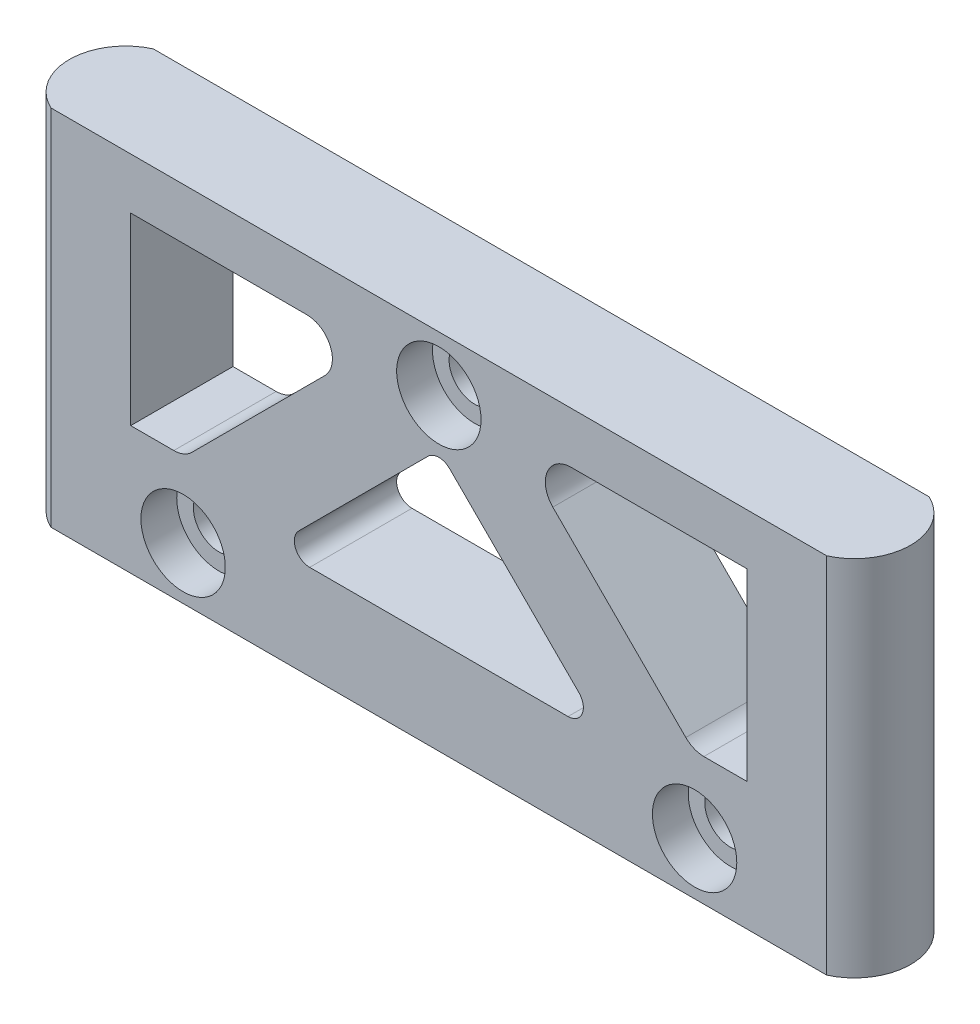
SolidWorks part; units mm, degrees
ref_plane "Front Plane" through (0, 0, 0) normal (0, 0, 1) x (1, 0, 0)
ref_plane "Top Plane" through (0, 0, 0) normal (0, 1, 0) x (1, 0, 0)
ref_plane "Right Plane" through (0, 0, 0) normal (1, 0, 0) x (0, 0, -1)
sketch "Sketch2" plane through (0, 0, 0) normal (0, 0, 1) x (1, 0, 0)
  line L0 (-100, 0) -> (0, 0) construction
  line L1 (-100, 10.25) -> (0, 10.25)
  line L2 (-100, -10.25) -> (0, -10.25)
  line L3 (0, 0) -> (-50, 50) construction
  line L4 (-7.2478, -7.2478) -> (-57.2478, 42.7522)
  line L5 (7.2478, 7.2478) -> (-42.7522, 57.2478)
  line L6 (-100, 0) -> (-50, 50) construction
  line L7 (-107.2478, 7.2478) -> (-57.2478, 57.2478)
  line L8 (-92.7522, -7.2478) -> (-42.7522, 42.7522)
  arc A0 (-100, 10.25) -> (-100, -10.25) centre (-100, 0) ccw
  arc A1 (0, -10.25) -> (0, 10.25) centre (0, 0) ccw
  arc A2 (-7.2478, -7.2478) -> (7.2478, 7.2478) centre (0, 0) ccw
  arc A3 (-42.7522, 57.2478) -> (-57.2478, 42.7522) centre (-50, 50) ccw
  arc A4 (-107.2478, 7.2478) -> (-92.7522, -7.2478) centre (-100, 0) ccw
  arc A5 (-42.7522, 42.7522) -> (-57.2478, 57.2478) centre (-50, 50) ccw
  point P3 (-50, 0)
  point P8 (-25, 25)
  point P15 (-75, 25)
  dimension "D1" = 100
  dimension "D2" = 20.5
  dimension "D3" = 45
  dimension "D4" = 45
extrude "Boss-Extrude4" add sketch "Sketch2" along normal blind 20 contours A4 L2 A2 L4 L1 L8 | A0 A4 L8 L1 | A3 L7 A0 L1 L8 L4 | L8 A5 A3 L4 | A5 L8 L4 L1 A1 L5 | L4 A2 A1 L1 region at (-74.0722, 27.272, 0) region at (-96.1173, 1.6083, 0) region at (-50, -1.0132, 0) region at (-25.9278, 27.272, 0) region at (-3.8827, 1.6083, 0) region at (-50, 49.2802, 0)
sketch "Sketch3" plane through (0, 0, 0) normal (0, 0, -1) x (-1, 0, 0)
  line L0 (57.2478, 57.2478) -> (107.2478, 7.2478)
  line L1 (57.2478, 57.2478) -> (107.2478, 7.2478)
  line L2 (100, -10.25) -> (0, -10.25)
  line L3 (100, -10.25) -> (0, -10.25)
  line L4 (-7.2478, 7.2478) -> (42.7522, 57.2478)
  line L5 (-7.2478, 7.2478) -> (42.7522, 57.2478)
  circle A0 centre (0, 0) radius 8.25
  circle A1 centre (50, 50) radius 8.25
  circle A2 centre (100, 0) radius 8.25
  arc A3 (100, -10.25) -> (107.2478, 7.2478) centre (100, 0) ccw
  arc A4 (100, -10.25) -> (107.2478, 7.2478) centre (100, 0) ccw
  arc A5 (-7.2478, 7.2478) -> (0, -10.25) centre (0, 0) ccw
  arc A6 (-7.2478, 7.2478) -> (0, -10.25) centre (0, 0) ccw
  arc A7 (57.2478, 57.2478) -> (42.7522, 57.2478) centre (50, 50) ccw
  arc A8 (57.2478, 57.2478) -> (42.7522, 57.2478) centre (50, 50) ccw
  dimension "D1" = 16.5
  dimension "D2" = 16.5
  dimension "D3" = 16.5
extrude "Cut-Extrude1" cut sketch "Sketch3" against normal blind 7 contours A0 | A1 | A2 region at (0, 0, 0) region at (-50, 50, 0) region at (-100, 0, 0)
sketch "Sketch4" plane through (0, 0, 20) normal (0, 0, 1) x (1, 0, 0)
  circle A0 centre (-100, 0) radius 8.25
  circle A1 centre (-50, 50) radius 8.25
  circle A2 centre (0, 0) radius 8.25
  arc A3 (-107.2478, 7.2478) -> (-100, -10.25) centre (-100, 0) ccw construction
  arc A4 (-42.7522, 57.2478) -> (-57.2478, 57.2478) centre (-50, 50) ccw construction
  arc A5 (0, -10.25) -> (7.2478, 7.2478) centre (0, 0) ccw construction
  dimension "D1" = 16.5
  dimension "D2" = 16.5
  dimension "D3" = 16.5
extrude "Cut-Extrude2" cut sketch "Sketch4" against normal blind 7
sketch "Sketch5" plane through (0, 0, 0) normal (0, 0, -1) x (-1, 0, 0)
  line L2 (17.5, 8.25) -> (50, 40.75)
  line L3 (50, 40.75) -> (82.5, 8.25)
  line L4 (82.5, 8.25) -> (17.5, 8.25)
  circle A0 centre (0, 0) radius 8.25 construction
  circle A2 centre (50, 50) radius 8.25 construction
  dimension "D3" = 45
  dimension "D1" = 9.25
  dimension "D2" = 45
extrude "Cut-Extrude3" cut sketch "Sketch5" against normal through all
sketch "Sketch6" plane through (0, 0, 20) normal (0, 0, 1) x (1, 0, 0)
  circle A1 centre (-100, 0) radius 5
  circle A2 centre (-50, 50) radius 5
  circle A3 centre (0, 0) radius 5
  circle A4 centre (-100, 0) radius 8.25 construction
  circle A6 centre (-50, 50) radius 8.25 construction
  circle A7 centre (0, 0) radius 8.25 construction
  dimension "D1" = 10
  dimension "D2" = 10
  dimension "D3" = 10
extrude "Cut-Extrude4" cut sketch "Sketch6" against normal blind 16.6
fillet "Fillet1" radius 3 3 edges at (-82.5, 8.25, 10) (-17.5, 8.25, 10) (-50, 40.75, 10)
sketch "Sketch7" plane through (0, 0, 0) normal (0, 0, -1) x (-1, 0, 0)
  line L0 (0, -10.25) -> (-10.25, -10.25)
  line L1 (-10.25, -10.25) -> (-10.25, 14.75)
  line L2 (-10.25, 14.75) -> (0.2543, 14.75)
  line L3 (-7.2478, 7.2478) -> (42.7522, 57.2478) construction
  line L7 (42.7522, 57.2478) -> (-7.2478, 7.2478)
  line L8 (0, -10.25) -> (100, -10.25)
  line L9 (107.2478, 7.2478) -> (57.2478, 57.2478)
  line L10 (42.7522, 57.2478) -> (-7.2478, 7.2478)
  line L11 (0, -10.25) -> (100, -10.25)
  line L12 (107.2478, 7.2478) -> (57.2478, 57.2478)
  arc A0 (-7.2478, 7.2478) -> (0, -10.25) centre (0, 0) ccw construction
  arc A4 (-7.2478, 7.2478) -> (0, -10.25) centre (0, 0) ccw
  arc A5 (100, -10.25) -> (107.2478, 7.2478) centre (100, 0) ccw
  arc A6 (57.2478, 57.2478) -> (42.7522, 57.2478) centre (50, 50) ccw
  arc A7 (-7.2478, 7.2478) -> (0, -10.25) centre (0, 0) ccw
  arc A8 (100, -10.25) -> (107.2478, 7.2478) centre (100, 0) ccw
  arc A9 (57.2478, 57.2478) -> (42.7522, 57.2478) centre (50, 50) ccw
  line M13 (42.7522, 57.2478) -> (-7.2478, 7.2478)
  arc M14 (-7.2478, 7.2478) -> (0, -10.25) centre (0, 0) ccw
  dimension "D1" = 25
  dimension "D2" = 0
extrude "Boss-Extrude5" add sketch "Sketch7" against normal blind 20 contours L2 L1 M14 M13 | L1 L0 M14 region at (7.9605, -7.9605, 0) region at (6.8621, 10.9629, 0)
sketch "Sketch8" plane through (0, 14.75, 0) normal (0, 1, 0) x (1, 0, 0)
  line L0 (10.25, -20) -> (10.25, 0) construction
  line L1 (10.25, -20) -> (-0.2543, -20) construction
  line L2 (10.25, -20) -> (20.2048, -20.9502)
  line L3 (10.25, 0) -> (20.2048, 0.9502)
  line L4 (10.25, 0) -> (10.25, -20)
  circle A0 centre (21.25, -10) radius 8.25
  circle A1 centre (21.25, -10) radius 11
  line M4 (10.25, -20) -> (10.25, 0)
  dimension "D1" = 16.5
  dimension "D2" = 22
  dimension "D3" = 10
extrude "Boss-Extrude6" add sketch "Sketch8" against normal blind 25 and the other way blind 46 contours A1 L3 L4 | A1 A0 | A1 L2 M4 region at (12.4438, 14.75, 18.0057) region at (13.3409, 14.75, 17.1901) region at (12.4438, 14.75, 1.9943)
sketch "Sketch9" plane through (10.25, 0, 0) normal (-1, 0, 0) x (0, 0, 1)
  line L1 (0, 60.75) -> (20, 60.75)
  line L2 (0, 60.75) -> (0, 50.75)
  line L3 (0, 50.75) -> (20, 50.75)
  line L4 (20, 60.75) -> (20, 50.75)
  line L5 (20, 60.75) -> (20, 14.75) construction
  line L6 (0, 60.75) -> (0, 14.75) construction
  line L7 (20, 60.75) -> (0, 60.75) construction
  dimension "D1" = 10
extrude "Boss-Extrude7" add sketch "Sketch9" along normal up to surface (56.5043 mm away) up to face at (-21.5032, 35.9989, 10)
fillet "Fillet2" radius 5 4 edges at (10.25, 2.25, 0) (10.25, 55.75, 0) (10.25, 55.75, 20) (10.25, 2.25, 20)
fillet "Fillet5" radius 5 2 edges at (-36.2543, 50.75, 10) (-0.2543, 14.75, 10)
sketch "Sketch10" plane through (0, 0, 0) normal (0, 0, -1) x (-1, 0, 0)
  line L0 (100, -10.25) -> (-10.0119, -10.25) construction
  line L1 (110.25, -10.25) -> (50, -10.25)
  line L2 (110.25, -10.25) -> (110.25, 60.25)
  line L3 (110.25, 60.25) -> (50, 60.25)
  line L4 (50, -10.25) -> (50, 60.25)
  arc A0 (57.2478, 57.2478) -> (42.7522, 57.2478) centre (50, 50) ccw construction
  arc A1 (100, -10.25) -> (107.2478, 7.2478) centre (100, 0) ccw construction
extrude "Cut-Extrude5" cut sketch "Sketch10" against normal through all
mirror "Mirror1" about plane through (-50, -10.25, 21) normal (1, 0, 0) of bodies 110
sketch "Sketch11" plane through (0, 0, 0) normal (0, 0, -1) x (-1, 0, 0)
  line L0 (46.2543, 60.75) -> (53.7457, 60.75)
  line L15 (-10.0119, -10.25) -> (110.0119, -10.25)
  line L16 (110.0119, -10.25) -> (110.0119, 14.75)
  line L17 (110.0119, 14.75) -> (101.8168, 14.75)
  line L18 (98.2812, 16.2145) -> (72.2812, 42.2145)
  line L19 (75.8168, 50.75) -> (110.0119, 50.75)
  line L20 (110.0119, 50.75) -> (110.0119, 60.75)
  line L21 (110.0119, 60.75) -> (53.7457, 60.75)
  line L22 (53.7457, 60.75) -> (57.2478, 57.2478)
  line L23 (42.7522, 57.2478) -> (46.2543, 60.75)
  line L24 (46.2543, 60.75) -> (-10.0119, 60.75)
  line L25 (-10.0119, 60.75) -> (-10.0119, 50.75)
  line L26 (-10.0119, 50.75) -> (24.1832, 50.75)
  line L27 (27.7188, 42.2145) -> (1.7188, 16.2145)
  line L28 (-1.8168, 14.75) -> (-10.0119, 14.75)
  line L29 (-10.0119, 14.75) -> (-10.0119, -10.25)
  line L30 (-10.0119, -10.25) -> (110.0119, -10.25)
  line L31 (110.0119, -10.25) -> (110.0119, 14.75)
  line L32 (110.0119, 14.75) -> (101.8168, 14.75)
  line L33 (98.2812, 16.2145) -> (72.2812, 42.2145)
  line L34 (75.8168, 50.75) -> (110.0119, 50.75)
  line L35 (110.0119, 50.75) -> (110.0119, 60.75)
  line L36 (110.0119, 60.75) -> (53.7457, 60.75)
  line L37 (53.7457, 60.75) -> (57.2478, 57.2478)
  line L38 (42.7522, 57.2478) -> (46.2543, 60.75)
  line L39 (46.2543, 60.75) -> (-10.0119, 60.75)
  line L40 (-10.0119, 60.75) -> (-10.0119, 50.75)
  line L41 (-10.0119, 50.75) -> (24.1832, 50.75)
  line L42 (27.7188, 42.2145) -> (1.7188, 16.2145)
  line L43 (-1.8168, 14.75) -> (-10.0119, 14.75)
  line L44 (-10.0119, 14.75) -> (-10.0119, -10.25)
  arc A5 (98.2812, 16.2145) -> (101.8168, 14.75) centre (101.8168, 19.75) ccw
  arc A6 (75.8168, 50.75) -> (72.2812, 42.2145) centre (75.8168, 45.75) ccw
  arc A7 (57.2478, 57.2478) -> (42.7522, 57.2478) centre (50, 50) ccw
  arc A8 (27.7188, 42.2145) -> (24.1832, 50.75) centre (24.1832, 45.75) ccw
  arc A9 (-1.8168, 14.75) -> (1.7188, 16.2145) centre (-1.8168, 19.75) ccw
  arc A10 (98.2812, 16.2145) -> (101.8168, 14.75) centre (101.8168, 19.75) ccw
  arc A11 (75.8168, 50.75) -> (72.2812, 42.2145) centre (75.8168, 45.75) ccw
  arc A12 (57.2478, 57.2478) -> (42.7522, 57.2478) centre (50, 50) ccw
  arc A13 (27.7188, 42.2145) -> (24.1832, 50.75) centre (24.1832, 45.75) ccw
  arc A14 (-1.8168, 14.75) -> (1.7188, 16.2145) centre (-1.8168, 19.75) ccw
  line M37 (53.7457, 60.75) -> (57.2478, 57.2478)
  arc M38 (57.2478, 57.2478) -> (42.7522, 57.2478) centre (50, 50) ccw
  line M39 (42.7522, 57.2478) -> (46.2543, 60.75)
  dimension "D1" = 0
extrude "Boss-Extrude8" add sketch "Sketch11" against normal blind 20 contours L0 M39 M38 M37 region at (-50, 60.6009, 0)
sketch "Sketch12" plane through (0, 60.75, 0) normal (0, 1, 0) x (1, 0, 0)
  circle A0 centre (-121.25, -10) radius 11
  circle A1 centre (21.25, -10) radius 11
  arc A2 (20.2048, -20.9502) -> (20.2048, 0.9502) centre (21.25, -10) ccw construction
  arc A3 (-120.2048, 0.9502) -> (-120.2048, -20.9502) centre (-121.25, -10) ccw construction
extrude "Boss-Extrude9" add sketch "Sketch12" against normal blind 20
sketch "Sketch13" plane through (0, 60.75, 0) normal (0, 1, 0) x (1, 0, 0)
  line L0 (-110.0119, 0) -> (10.0119, 0) construction
  line L1 (-132.25, 0) -> (32.25, 0)
  line L2 (-132.25, 0) -> (-132.25, -20)
  line L3 (-132.25, -20) -> (32.25, -20)
  line L4 (32.25, 0) -> (32.25, -20)
  line L5 (-110.0119, -20) -> (10.0119, -20) construction
  arc A0 (-120.2048, 0.9502) -> (-120.2048, -20.9502) centre (-121.25, -10) ccw construction
  arc A1 (20.2048, -20.9502) -> (20.2048, 0.9502) centre (21.25, -10) ccw construction
extrude "Cut-Extrude6" cut sketch "Sketch13" against normal through all flip side to cut
equation "\"D4@Sketch2\"=\"D3@Sketch2\""
equation "\"D2@Sketch3\"=\"D1@Sketch3\""
equation "\"D3@Sketch3\"=\"D1@Sketch3\""
equation "\"D2@Sketch4\"=\"D1@Sketch4\""
equation "\"D3@Sketch4\"=\"D1@Sketch4\""
equation "\"D3@Sketch5\"=\"D2@Sketch5\""
equation "\"D2@Sketch6\"=\"D1@Sketch6\""
equation "\"D3@Sketch6\"=\"D2@Sketch6\""
